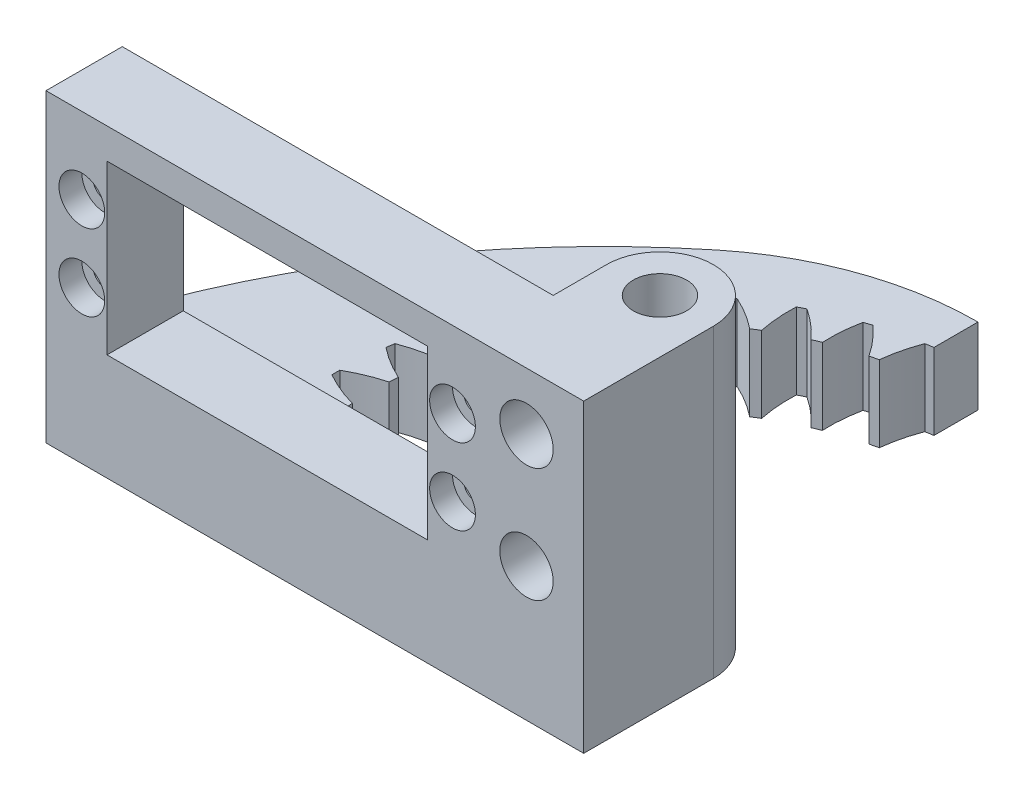
SolidWorks part; units mm, degrees
material "ABS"
ref_plane "Front Plane" through (0, 0, 0) normal (0, 0, 1) x (1, 0, 0)
ref_plane "Top Plane" through (0, 0, 0) normal (0, 1, 0) x (1, 0, 0)
ref_plane "Right Plane" through (0, 0, 0) normal (1, 0, 0) x (0, 0, -1)
ref_axis "X" through (-32.525, 0, 0) along (1, 0, 0)
ref_axis "Y" through (0, 17, 0) along (0, -1, 0)
ref_axis "Z" through (0, 0, -48.1921) along (0, 0, 1)
sketch "Sketch1" plane through (0, 0, 0) normal (0, 0, 1) x (1, 0, 0)
  line L0 (34, -7.5) -> (34, 7.5) construction
  line L1 (0, 0) -> (34, 0) construction
  line L2 (24.3, 5) -> (24.3, -5) construction
  line L3 (-21, 11) -> (21, 11)
  line L4 (-21, 11) -> (-21, -11)
  line L5 (-21, -11) -> (21, -11)
  line L6 (21, 11) -> (21, -11)
  line L7 (-21, 11) -> (21, -11) construction
  line L8 (-21, -11) -> (21, 11) construction
  line L9 (0, 0) -> (0, 11) construction
  line L10 (34, -15) -> (-29, -15)
  line L11 (-29, -15) -> (-29, 15)
  line L12 (-29, 15) -> (34, 15)
  line L13 (41.5, 7.5) -> (41.5, -7.5)
  line L14 (34, 0) -> (41.5, 0) construction
  line L15 (34, -15) -> (41.5, -15)
  line L16 (41.5, -15) -> (41.5, -7.5)
  line L17 (34, 15) -> (41.5, 15)
  line L18 (41.5, 15) -> (41.5, 7.5)
  circle A0 centre (34, -7.5) radius 3.5
  circle A1 centre (34, 7.5) radius 3.5
  circle A2 centre (24.3, 5) radius 1.5
  circle A3 centre (24.3, -5) radius 1.5
  circle A4 centre (-24.3, -5) radius 1.5
  circle A5 centre (-24.3, 5) radius 1.5
  arc A6 (34, 15) -> (41.5, 7.5) centre (34, 7.5) cw construction
  arc A7 (41.5, -7.5) -> (34, -15) centre (34, -7.5) cw construction
  point P14 (24.3, 0)
  dimension "D1" = 22
  dimension "D4" = 7
  dimension "D6" = 3
  dimension "D7" = 24.3
  dimension "D10" = 4
  dimension "D2" = 42
  dimension "D3" = 34
  dimension "D5" = 15
  dimension "D8" = 10
  dimension "D9" = 10
  dimension "D11" = 8
extrude "Boss-Extrude1" add sketch "Sketch1" along normal blind 10
sketch "Sketch2" plane through (0, 0, 0) normal (0, 0, 1) x (1, 0, 0)
  circle A0 centre (-24.3, 5) radius 3
  circle A1 centre (-24.3, -5) radius 3
  circle A2 centre (24.3, 5) radius 3
  circle A3 centre (24.3, -5) radius 3
  dimension "D1" = 6
extrude "Cut-Extrude1" cut sketch "Sketch2" against normal blind 3 from surface starting at face at (-25.8, -5, 10)
sketch "Sketch4" plane through (0, 0, 0) normal (0, 1, 0) x (1, 0, 0)
  line L0 (41.5, 0) -> (41.5, 7)
  line L1 (34, 0) -> (41.5, 0) construction
  line L2 (27.5, 7) -> (27.5, 0)
  line L3 (34, 0) -> (-29, 0) construction
  line L4 (0, 0) -> (34, 0) construction
  line L5 (41.5, 0) -> (27.5, 0)
  line L6 (-29, 0) -> (27.5, 0)
  line L7 (41.5, 0) -> (41.5, -10)
  line L8 (41.5, -10) -> (-29, -10)
  line L9 (-29, -10) -> (-29, 0)
  line L10 (3.0686, 45.8853) -> (6.2117, 41.9968)
  line L11 (3.0686, 45.8853) -> (6.9571, 49.0284) construction
  arc A0 (41.5, 7) -> (27.5, 7) centre (34.5, 7) ccw
  circle A1 centre (34.5, 7) radius 5
  arc A2 (41.5, 7) -> (27.5, 7) centre (34.5, 7) cw construction
  arc A3 (-9.9522, 0) -> (6.2117, 41.9968) centre (34.5, 7) cw
  arc A4 (3.0686, 45.8853) -> (-29, 0) centre (66.5114, -32.6028) ccw
  dimension "D1" = 10
  dimension "D2" = 2
  dimension "D3" = 45
  dimension "D4" = 5
  dimension "D6" = 5
  dimension "D5" = 60
extrude "Boss-Extrude2" add sketch "Sketch4" against normal blind 10 from surface contours L0 A0 L2 L5 A1 | L9 L8 L7 L5 L6 | L6 A3 L10 region at (34.5, 0, -0.198) region at (6.25, 0, 5) region at (-13.2311, 0, -18.1531) starting at face at (6.25, -15, 5)
extrude "Boss-Extrude3" add sketch "Sketch4<3>" along normal up to surface and the other way up to surface contours L0 A0 L2 L5 A1 region at (34.5, 0, -0.198) up to face at (6.25, 15, 5) other way up to face at (34.5, -15, -2)
sketch "Sketch4<3>" plane through (0, 0, 0) normal (0, 1, 0) x (1, 0, 0) same geometry as "Sketch4"
extrude "Boss-Extrude4" add sketch "Sketch1<3>" along normal offset from surface (4 mm away) 6 contours A1 | A0 region at (34, -7.5, 0) region at (34, 7.5, 0) up to face at (-21.3, -5, 10)
sketch "Sketch1<3>" plane through (0, 0, 0) normal (0, 0, 1) x (1, 0, 0) same geometry as "Sketch1"
sketch "Sketch5" plane through (0, 0, 0) normal (0, 1, 0) x (1, 0, 0)
  line L0 (34, 0) -> (-29, 0) construction
  line L1 (-7.5563, 0) -> (-29, 0)
  line L4 (3.0686, 45.8853) -> (6.2117, 41.9968) construction
  line L5 (3.0686, 45.8853) -> (6.2117, 41.9968) construction
  line L6 (-7.5563, 0) -> (-7.5563, 0.868)
  line L7 (28.368, 51.5802) -> (28.368, 54.8316)
  line L8 (28.368, 49.0563) -> (28.368, 51.5802)
  arc A2 (3.0686, 45.8853) -> (-29, 0) centre (66.5114, -32.6028) ccw construction
  arc A3 (3.0686, 45.8853) -> (-29, 0) centre (66.5114, -32.6028) ccw
  arc A229 (6.2117, 41.9968) -> (28.368, 51.5802) centre (34.5, 7) cw construction
  arc A643 (28.368, 54.8316) -> (3.0686, 45.8853) centre (28.368, 14.5862) ccw
  arc A644 (6.2117, 41.9968) -> (-9.9522, 0) centre (34.5, 7) ccw construction
  circle A645 centre (34.5, 7) radius 45 construction
  arc A802 (38.0421, -30.8346) -> (40.632, -35.0563) centre (56.2536, -22.5676) ccw
  arc A803 (36.9201, -30.9229) -> (38.0421, -30.8346) centre (34.5, 7) ccw
  arc A804 (35.0225, -35.4978) -> (36.9201, -30.9229) centre (17.6396, -25.6066) ccw
  arc A805 (33.9775, -35.4978) -> (35.0225, -35.4978) centre (34.5, 7) ccw
  arc A806 (32.0799, -30.9229) -> (33.9775, -35.4978) centre (51.3604, -25.6066) ccw
  arc A807 (30.9579, -30.8346) -> (32.0799, -30.9229) centre (34.5, 7) ccw
  arc A808 (28.368, -35.0563) -> (30.9579, -30.8346) centre (12.7464, -22.5676) ccw
  arc A809 (27.3358, -34.8928) -> (28.368, -35.0563) centre (34.5, 7) ccw
  arc A810 (26.1772, -30.0774) -> (27.3358, -34.8928) centre (46.052, -27.8427) ccw
  arc A811 (25.0829, -29.8146) -> (26.1772, -30.0774) centre (34.5, 7) ccw
  arc A812 (21.8644, -33.5793) -> (25.0829, -29.8146) centre (8.3889, -18.8006) ccw
  arc A813 (20.8705, -33.2563) -> (21.8644, -33.5793) centre (34.5, 7) ccw
  arc A814 (20.4795, -28.3189) -> (20.8705, -33.2563) centre (40.4592, -29.2209) ccw
  arc A815 (19.4397, -27.8882) -> (20.4795, -28.3189) centre (34.5, 7) ccw
  arc A816 (15.672, -31.103) -> (19.4397, -27.8882) centre (4.6742, -14.3983) ccw
  arc A817 (14.7408, -30.6286) -> (15.672, -31.103) centre (34.5, 7) ccw
  arc A818 (15.127, -25.6908) -> (14.7408, -30.6286) centre (34.7196, -29.7071) ccw
  arc A819 (14.1674, -25.1028) -> (15.127, -25.6908) centre (34.5, 7) ccw
  arc A820 (9.9432, -27.6886) -> (14.1674, -25.1028) centre (1.694, -9.469) ccw
  arc A821 (9.0977, -27.0743) -> (9.9432, -27.6886) centre (34.5, 7) ccw
  arc A822 (10.2516, -22.2577) -> (9.0977, -27.0743) centre (28.9746, -29.2896) ccw
  arc A823 (9.3958, -21.5268) -> (10.2516, -22.2577) centre (34.5, 7) ccw
  arc A824 (4.819, -23.42) -> (9.3958, -21.5268) centre (-0.4784, -4.1343) ccw
  arc A825 (4.08, -22.681) -> (4.819, -23.42) centre (34.5, 7) ccw
  arc A826 (5.9732, -18.1042) -> (4.08, -22.681) centre (23.3657, -27.9784) ccw
  arc A827 (5.2423, -17.2484) -> (5.9732, -18.1042) centre (34.5, 7) ccw
  arc A828 (0.4257, -18.4023) -> (5.2423, -17.2484) centre (-1.7896, 1.4746) ccw
  arc A829 (-0.1886, -17.5568) -> (0.4257, -18.4023) centre (34.5, 7) ccw
  arc A830 (2.3972, -13.3326) -> (-0.1886, -17.5568) centre (18.031, -25.806) ccw
  arc A831 (1.8092, -12.373) -> (2.3972, -13.3326) centre (34.5, 7) ccw
  arc A832 (-3.1286, -12.7592) -> (1.8092, -12.373) centre (-2.2071, 7.2196) ccw
  arc A833 (-3.603, -11.828) -> (-3.1286, -12.7592) centre (34.5, 7) ccw
  arc A834 (-0.3882, -8.0603) -> (-3.603, -11.828) centre (13.1017, -22.8258) ccw
  arc A835 (-0.8189, -7.0205) -> (-0.3882, -8.0603) centre (34.5, 7) ccw
  arc A836 (-5.7563, -6.6295) -> (-0.8189, -7.0205) centre (-1.7209, 12.9592) ccw
  arc A837 (-6.0793, -5.6356) -> (-5.7563, -6.6295) centre (34.5, 7) ccw
  arc A838 (-2.3146, -2.4171) -> (-6.0793, -5.6356) centre (8.6994, -19.1111) ccw
  arc A839 (-2.5774, -1.3228) -> (-2.3146, -2.4171) centre (34.5, 7) ccw
  arc A840 (-7.3928, -0.1642) -> (-2.5774, -1.3228) centre (-0.3427, 18.552) ccw
  arc A841 (-7.5563, 0.868) -> (-7.3928, -0.1642) centre (34.5, 7) ccw
  arc A842 (-3.3346, 3.4579) -> (-7.5563, 0.868) centre (4.9324, -14.7536) ccw
  arc A843 (-3.4229, 4.5799) -> (-3.3346, 3.4579) centre (34.5, 7) ccw
  arc A844 (-7.9978, 6.4775) -> (-3.4229, 4.5799) centre (1.8934, 23.8604) ccw
  arc A845 (-7.9978, 7.5225) -> (-7.9978, 6.4775) centre (34.5, 7) ccw
  arc A846 (-3.4229, 9.4201) -> (-7.9978, 7.5225) centre (1.8934, -9.8604) ccw
  arc A847 (-3.3346, 10.5421) -> (-3.4229, 9.4201) centre (34.5, 7) ccw
  arc A848 (-7.5563, 13.132) -> (-3.3346, 10.5421) centre (4.9324, 28.7536) ccw
  arc A849 (-7.3928, 14.1642) -> (-7.5563, 13.132) centre (34.5, 7) ccw
  arc A850 (-2.5774, 15.3228) -> (-7.3928, 14.1642) centre (-0.3427, -4.552) ccw
  arc A851 (-2.3146, 16.4171) -> (-2.5774, 15.3228) centre (34.5, 7) ccw
  arc A852 (-6.0793, 19.6356) -> (-2.3146, 16.4171) centre (8.6994, 33.1111) ccw
  arc A853 (-5.7563, 20.6295) -> (-6.0793, 19.6356) centre (34.5, 7) ccw
  arc A854 (-0.8189, 21.0205) -> (-5.7563, 20.6295) centre (-1.7209, 1.0408) ccw
  arc A855 (-0.3882, 22.0603) -> (-0.8189, 21.0205) centre (34.5, 7) ccw
  arc A856 (-3.603, 25.828) -> (-0.3882, 22.0603) centre (13.1017, 36.8258) ccw
  arc A857 (-3.1286, 26.7592) -> (-3.603, 25.828) centre (34.5, 7) ccw
  arc A858 (1.8092, 26.373) -> (-3.1286, 26.7592) centre (-2.2071, 6.7804) ccw
  arc A859 (2.3972, 27.3326) -> (1.8092, 26.373) centre (34.5, 7) ccw
  arc A860 (-0.1886, 31.5568) -> (2.3972, 27.3326) centre (18.031, 39.806) ccw
  arc A861 (0.4257, 32.4023) -> (-0.1886, 31.5568) centre (34.5, 7) ccw
  arc A862 (5.2423, 31.2484) -> (0.4257, 32.4023) centre (-1.7896, 12.5254) ccw
  arc A863 (5.9732, 32.1042) -> (5.2423, 31.2484) centre (34.5, 7) ccw
  arc A864 (4.08, 36.681) -> (5.9732, 32.1042) centre (23.3657, 41.9784) ccw
  arc A865 (4.819, 37.42) -> (4.08, 36.681) centre (34.5, 7) ccw
  arc A866 (9.3958, 35.5268) -> (4.819, 37.42) centre (-0.4784, 18.1343) ccw
  arc A867 (10.2516, 36.2577) -> (9.3958, 35.5268) centre (34.5, 7) ccw
  arc A868 (9.0977, 41.0743) -> (10.2516, 36.2577) centre (28.9746, 43.2896) ccw
  arc A869 (9.9432, 41.6886) -> (9.0977, 41.0743) centre (34.5, 7) ccw
  arc A870 (14.1674, 39.1028) -> (9.9432, 41.6886) centre (1.694, 23.469) ccw
  arc A871 (15.127, 39.6908) -> (14.1674, 39.1028) centre (34.5, 7) ccw
  arc A872 (14.7408, 44.6286) -> (15.127, 39.6908) centre (34.7196, 43.7071) ccw
  arc A873 (15.672, 45.103) -> (14.7408, 44.6286) centre (34.5, 7) ccw
  arc A874 (19.4397, 41.8882) -> (15.672, 45.103) centre (4.6742, 28.3983) ccw
  arc A875 (20.4795, 42.3189) -> (19.4397, 41.8882) centre (34.5, 7) ccw
  arc A876 (20.8705, 47.2563) -> (20.4795, 42.3189) centre (40.4592, 43.2209) ccw
  arc A877 (21.8644, 47.5793) -> (20.8705, 47.2563) centre (34.5, 7) ccw
  arc A878 (25.0829, 43.8146) -> (21.8644, 47.5793) centre (8.3889, 32.8006) ccw
  arc A879 (26.1772, 44.0774) -> (25.0829, 43.8146) centre (34.5, 7) ccw
  arc A880 (27.3358, 48.8928) -> (26.1772, 44.0774) centre (46.052, 41.8427) ccw
  arc A881 (28.368, 49.0563) -> (27.3358, 48.8928) centre (34.5, 7) ccw
  arc A882 (30.9579, 44.8346) -> (28.368, 49.0563) centre (12.7464, 36.5676) ccw
  arc A883 (32.0799, 44.9229) -> (30.9579, 44.8346) centre (34.5, 7) ccw
  arc A884 (33.9775, 49.4978) -> (32.0799, 44.9229) centre (51.3604, 39.6066) ccw
  arc A885 (35.0225, 49.4978) -> (33.9775, 49.4978) centre (34.5, 7) ccw
  arc A886 (36.9201, 44.9229) -> (35.0225, 49.4978) centre (17.6396, 39.6066) ccw
  arc A887 (38.0421, 44.8346) -> (36.9201, 44.9229) centre (34.5, 7) ccw
  arc A888 (40.632, 49.0563) -> (38.0421, 44.8346) centre (56.2536, 36.5676) ccw
  arc A889 (41.6642, 48.8928) -> (40.632, 49.0563) centre (34.5, 7) ccw
  arc A890 (42.8228, 44.0774) -> (41.6642, 48.8928) centre (22.948, 41.8427) ccw
  arc A891 (43.9171, 43.8146) -> (42.8228, 44.0774) centre (34.5, 7) ccw
  arc A892 (47.1356, 47.5793) -> (43.9171, 43.8146) centre (60.6111, 32.8006) ccw
  arc A893 (48.1295, 47.2563) -> (47.1356, 47.5793) centre (34.5, 7) ccw
  arc A894 (48.5205, 42.3189) -> (48.1295, 47.2563) centre (28.5408, 43.2209) ccw
  arc A895 (49.5603, 41.8882) -> (48.5205, 42.3189) centre (34.5, 7) ccw
  arc A896 (53.328, 45.103) -> (49.5603, 41.8882) centre (64.3258, 28.3983) ccw
  arc A897 (54.2592, 44.6286) -> (53.328, 45.103) centre (34.5, 7) ccw
  arc A898 (53.873, 39.6908) -> (54.2592, 44.6286) centre (34.2804, 43.7071) ccw
  arc A899 (54.8326, 39.1028) -> (53.873, 39.6908) centre (34.5, 7) ccw
  arc A900 (59.0568, 41.6886) -> (54.8326, 39.1028) centre (67.306, 23.469) ccw
  arc A901 (59.9023, 41.0743) -> (59.0568, 41.6886) centre (34.5, 7) ccw
  arc A902 (58.7484, 36.2577) -> (59.9023, 41.0743) centre (40.0254, 43.2896) ccw
  arc A903 (59.6042, 35.5268) -> (58.7484, 36.2577) centre (34.5, 7) ccw
  arc A904 (64.181, 37.42) -> (59.6042, 35.5268) centre (69.4784, 18.1343) ccw
  arc A905 (64.92, 36.681) -> (64.181, 37.42) centre (34.5, 7) ccw
  arc A906 (63.0268, 32.1042) -> (64.92, 36.681) centre (45.6343, 41.9784) ccw
  arc A907 (63.7577, 31.2484) -> (63.0268, 32.1042) centre (34.5, 7) ccw
  arc A908 (68.5743, 32.4023) -> (63.7577, 31.2484) centre (70.7896, 12.5254) ccw
  arc A909 (69.1886, 31.5568) -> (68.5743, 32.4023) centre (34.5, 7) ccw
  arc A910 (66.6028, 27.3326) -> (69.1886, 31.5568) centre (50.969, 39.806) ccw
  arc A911 (67.1908, 26.373) -> (66.6028, 27.3326) centre (34.5, 7) ccw
  arc A912 (72.1286, 26.7592) -> (67.1908, 26.373) centre (71.2071, 6.7804) ccw
  arc A913 (72.603, 25.828) -> (72.1286, 26.7592) centre (34.5, 7) ccw
  arc A914 (69.3882, 22.0603) -> (72.603, 25.828) centre (55.8983, 36.8258) ccw
  arc A915 (69.8189, 21.0205) -> (69.3882, 22.0603) centre (34.5, 7) ccw
  arc A916 (74.7563, 20.6295) -> (69.8189, 21.0205) centre (70.7209, 1.0408) ccw
  arc A917 (75.0793, 19.6356) -> (74.7563, 20.6295) centre (34.5, 7) ccw
  arc A918 (71.3146, 16.4171) -> (75.0793, 19.6356) centre (60.3006, 33.1111) ccw
  arc A919 (71.5774, 15.3228) -> (71.3146, 16.4171) centre (34.5, 7) ccw
  arc A920 (76.3928, 14.1642) -> (71.5774, 15.3228) centre (69.3427, -4.552) ccw
  arc A921 (76.5563, 13.132) -> (76.3928, 14.1642) centre (34.5, 7) ccw
  arc A922 (72.3346, 10.5421) -> (76.5563, 13.132) centre (64.0676, 28.7536) ccw
  arc A923 (72.4229, 9.4201) -> (72.3346, 10.5421) centre (34.5, 7) ccw
  arc A924 (76.9978, 7.5225) -> (72.4229, 9.4201) centre (67.1066, -9.8604) ccw
  arc A925 (76.9978, 6.4775) -> (76.9978, 7.5225) centre (34.5, 7) ccw
  arc A926 (72.4229, 4.5799) -> (76.9978, 6.4775) centre (67.1066, 23.8604) ccw
  arc A927 (72.3346, 3.4579) -> (72.4229, 4.5799) centre (34.5, 7) ccw
  arc A928 (76.5563, 0.868) -> (72.3346, 3.4579) centre (64.0676, -14.7536) ccw
  arc A929 (76.3928, -0.1642) -> (76.5563, 0.868) centre (34.5, 7) ccw
  arc A930 (71.5774, -1.3228) -> (76.3928, -0.1642) centre (69.3427, 18.552) ccw
  arc A931 (71.3146, -2.4171) -> (71.5774, -1.3228) centre (34.5, 7) ccw
  arc A932 (75.0793, -5.6356) -> (71.3146, -2.4171) centre (60.3006, -19.1111) ccw
  arc A933 (74.7563, -6.6295) -> (75.0793, -5.6356) centre (34.5, 7) ccw
  arc A934 (69.8189, -7.0205) -> (74.7563, -6.6295) centre (70.7209, 12.9592) ccw
  arc A935 (69.3882, -8.0603) -> (69.8189, -7.0205) centre (34.5, 7) ccw
  arc A936 (72.603, -11.828) -> (69.3882, -8.0603) centre (55.8983, -22.8258) ccw
  arc A937 (72.1286, -12.7592) -> (72.603, -11.828) centre (34.5, 7) ccw
  arc A938 (67.1908, -12.373) -> (72.1286, -12.7592) centre (71.2071, 7.2196) ccw
  arc A939 (66.6028, -13.3326) -> (67.1908, -12.373) centre (34.5, 7) ccw
  arc A940 (69.1886, -17.5568) -> (66.6028, -13.3326) centre (50.969, -25.806) ccw
  arc A941 (68.5743, -18.4023) -> (69.1886, -17.5568) centre (34.5, 7) ccw
  arc A942 (63.7577, -17.2484) -> (68.5743, -18.4023) centre (70.7896, 1.4746) ccw
  arc A943 (63.0268, -18.1042) -> (63.7577, -17.2484) centre (34.5, 7) ccw
  arc A944 (64.92, -22.681) -> (63.0268, -18.1042) centre (45.6343, -27.9784) ccw
  arc A945 (64.181, -23.42) -> (64.92, -22.681) centre (34.5, 7) ccw
  arc A946 (59.6042, -21.5268) -> (64.181, -23.42) centre (69.4784, -4.1343) ccw
  arc A947 (58.7484, -22.2577) -> (59.6042, -21.5268) centre (34.5, 7) ccw
  arc A948 (59.9023, -27.0743) -> (58.7484, -22.2577) centre (40.0254, -29.2896) ccw
  arc A949 (59.0568, -27.6886) -> (59.9023, -27.0743) centre (34.5, 7) ccw
  arc A950 (54.8326, -25.1028) -> (59.0568, -27.6886) centre (67.306, -9.469) ccw
  arc A951 (53.873, -25.6908) -> (54.8326, -25.1028) centre (34.5, 7) ccw
  arc A952 (54.2592, -30.6286) -> (53.873, -25.6908) centre (34.2804, -29.7071) ccw
  arc A953 (53.328, -31.103) -> (54.2592, -30.6286) centre (34.5, 7) ccw
  arc A954 (49.5603, -27.8882) -> (53.328, -31.103) centre (64.3258, -14.3983) ccw
  arc A955 (48.5205, -28.3189) -> (49.5603, -27.8882) centre (34.5, 7) ccw
  arc A956 (48.1295, -33.2563) -> (48.5205, -28.3189) centre (28.5408, -29.2209) ccw
  arc A957 (47.1356, -33.5793) -> (48.1295, -33.2563) centre (34.5, 7) ccw
  arc A958 (43.9171, -29.8146) -> (47.1356, -33.5793) centre (60.6111, -18.8006) ccw
  arc A959 (42.8228, -30.0774) -> (43.9171, -29.8146) centre (34.5, 7) ccw
  arc A960 (41.6642, -34.8928) -> (42.8228, -30.0774) centre (22.948, -27.8427) ccw
  arc A961 (40.632, -35.0563) -> (41.6642, -34.8928) centre (34.5, 7) ccw
  arc A1002 (-3.3346, 3.4579) -> (-7.5563, 0.868) centre (4.9324, -14.7536) ccw
  arc A1003 (-3.4229, 4.5799) -> (-3.3346, 3.4579) centre (34.5, 7) ccw
  arc A1004 (-7.9978, 6.4775) -> (-3.4229, 4.5799) centre (1.8934, 23.8604) ccw
  arc A1005 (-7.9978, 7.5225) -> (-7.9978, 6.4775) centre (34.5, 7) ccw
  arc A1006 (-3.4229, 9.4201) -> (-7.9978, 7.5225) centre (1.8934, -9.8604) ccw
  arc A1007 (-3.3346, 10.5421) -> (-3.4229, 9.4201) centre (34.5, 7) ccw
  arc A1008 (-7.5563, 13.132) -> (-3.3346, 10.5421) centre (4.9324, 28.7536) ccw
  arc A1009 (-7.3928, 14.1642) -> (-7.5563, 13.132) centre (34.5, 7) ccw
  arc A1010 (-2.5774, 15.3228) -> (-7.3928, 14.1642) centre (-0.3427, -4.552) ccw
  arc A1011 (-2.3146, 16.4171) -> (-2.5774, 15.3228) centre (34.5, 7) ccw
  arc A1012 (-6.0793, 19.6356) -> (-2.3146, 16.4171) centre (8.6994, 33.1111) ccw
  arc A1013 (-5.7563, 20.6295) -> (-6.0793, 19.6356) centre (34.5, 7) ccw
  arc A1014 (-0.8189, 21.0205) -> (-5.7563, 20.6295) centre (-1.7209, 1.0408) ccw
  arc A1015 (-0.3882, 22.0603) -> (-0.8189, 21.0205) centre (34.5, 7) ccw
  arc A1016 (-3.603, 25.828) -> (-0.3882, 22.0603) centre (13.1017, 36.8258) ccw
  arc A1017 (-3.1286, 26.7592) -> (-3.603, 25.828) centre (34.5, 7) ccw
  arc A1018 (1.8092, 26.373) -> (-3.1286, 26.7592) centre (-2.2071, 6.7804) ccw
  arc A1019 (2.3972, 27.3326) -> (1.8092, 26.373) centre (34.5, 7) ccw
  arc A1020 (-0.1886, 31.5568) -> (2.3972, 27.3326) centre (18.031, 39.806) ccw
  arc A1021 (0.4257, 32.4023) -> (-0.1886, 31.5568) centre (34.5, 7) ccw
  arc A1022 (5.2423, 31.2484) -> (0.4257, 32.4023) centre (-1.7896, 12.5254) ccw
  arc A1023 (5.9732, 32.1042) -> (5.2423, 31.2484) centre (34.5, 7) ccw
  arc A1024 (4.08, 36.681) -> (5.9732, 32.1042) centre (23.3657, 41.9784) ccw
  arc A1025 (4.819, 37.42) -> (4.08, 36.681) centre (34.5, 7) ccw
  arc A1026 (9.3958, 35.5268) -> (4.819, 37.42) centre (-0.4784, 18.1343) ccw
  arc A1027 (10.2516, 36.2577) -> (9.3958, 35.5268) centre (34.5, 7) ccw
  arc A1028 (9.0977, 41.0743) -> (10.2516, 36.2577) centre (28.9746, 43.2896) ccw
  arc A1029 (9.9432, 41.6886) -> (9.0977, 41.0743) centre (34.5, 7) ccw
  arc A1030 (14.1674, 39.1028) -> (9.9432, 41.6886) centre (1.694, 23.469) ccw
  arc A1031 (15.127, 39.6908) -> (14.1674, 39.1028) centre (34.5, 7) ccw
  arc A1032 (14.7408, 44.6286) -> (15.127, 39.6908) centre (34.7196, 43.7071) ccw
  arc A1033 (15.672, 45.103) -> (14.7408, 44.6286) centre (34.5, 7) ccw
  arc A1034 (19.4397, 41.8882) -> (15.672, 45.103) centre (4.6742, 28.3983) ccw
  arc A1035 (20.4795, 42.3189) -> (19.4397, 41.8882) centre (34.5, 7) ccw
  arc A1036 (20.8705, 47.2563) -> (20.4795, 42.3189) centre (40.4592, 43.2209) ccw
  arc A1037 (21.8644, 47.5793) -> (20.8705, 47.2563) centre (34.5, 7) ccw
  arc A1038 (25.0829, 43.8146) -> (21.8644, 47.5793) centre (8.3889, 32.8006) ccw
  arc A1039 (26.1772, 44.0774) -> (25.0829, 43.8146) centre (34.5, 7) ccw
  arc A1040 (27.3358, 48.8928) -> (26.1772, 44.0774) centre (46.052, 41.8427) ccw
  arc A1041 (28.368, 49.0563) -> (27.3358, 48.8928) centre (34.5, 7) ccw
  point P25 (28.368, 51.9946)
  dimension "D1" = 0
extrude "Boss-Extrude5" add sketch "Sketch5" against normal up to surface (25 mm away) from surface up to face at (34.5, -25, -2) starting at face at (-9.6359, -15, -23.0789)
sketch "Sketch6" plane through (0, 0, 0) normal (0, 1, 0) x (1, 0, 0)
  circle A0 centre (34.5, 7) radius 5 construction
  circle A1 centre (34.5, 7) radius 5
  circle A2 centre (34.5, 7) radius 3.5
  dimension "D1" = 7
extrude "Boss-Extrude6" add sketch "Sketch6" along normal up to surface (15 mm away) and the other way up to surface (25 mm away) up to face at (13.3333, 15, -0.1667) other way up to face at (34.5, -25, -2)
extrude "Boss-Extrude7" add sketch "Sketch6<2>" along normal offset from surface 6 and the other way offset from surface 6 contours A2 up to face at (13.3333, 15, -0.1667) other way up to face at (6.6937, -25, -25.757)
sketch "Sketch6<2>" plane through (0, 0, 0) normal (0, 1, 0) x (1, 0, 0) same geometry as "Sketch6"
ref_axis "Axis1" through (34.5, 15, -7) along (0, -1, 0)
